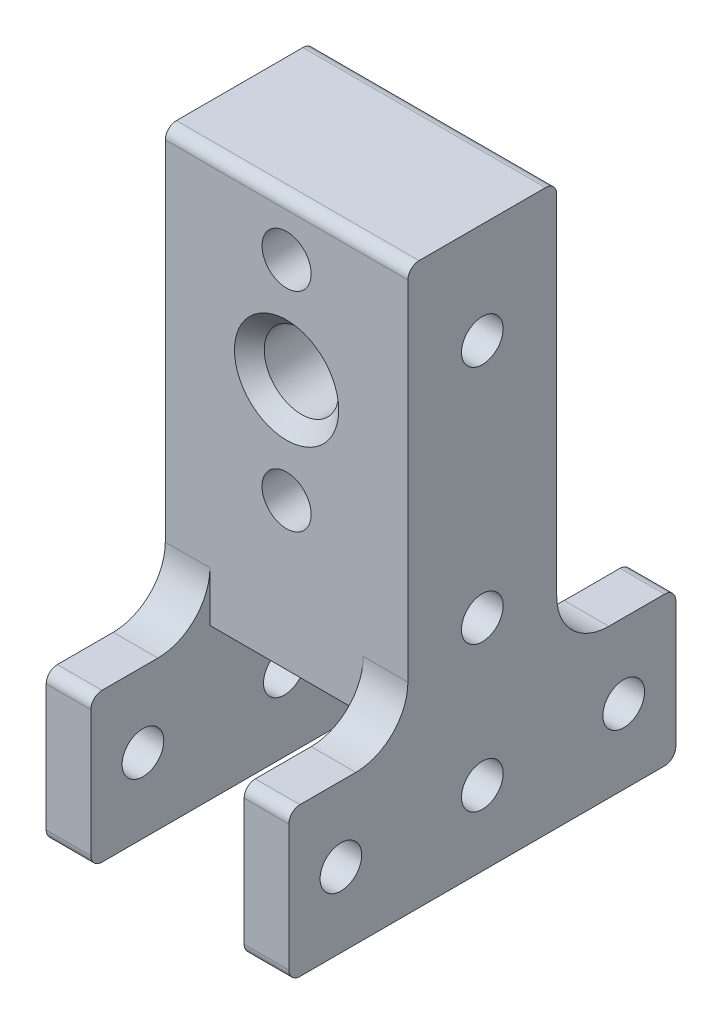
SolidWorks part; units mm, degrees
ref_plane "Front plane" through (0, 0, 0) normal (0, 0, 1) x (1, 0, 0)
ref_plane "Top plane" through (0, 0, 0) normal (0, 1, 0) x (1, 0, 0)
ref_plane "Right plane" through (0, 0, 0) normal (1, 0, 0) x (0, 0, -1)
ref_axis "Axis X" through (0, 0, 0) along (1, 0, 0)
ref_axis "Axis Y" through (0, 0, 0) along (0, 1, 0)
ref_axis "Axis Z" through (0, 0, 0) along (0, 0, 1)
sketch "Sketch1" plane through (0, 0, 0) normal (1, 0, 0) x (0, 0, -1)
  line L1 (10, 65.3) -> (-10, 65.3)
  line L2 (10, 65.3) -> (10, 10.3)
  line L3 (10, 10.3) -> (-10, 10.3)
  line L4 (-10, 65.3) -> (-10, 10.3)
  line L5 (10, 65.3) -> (-10, 10.3) construction
  line L6 (10, 10.3) -> (-10, 65.3) construction
  point P0 (0, 37.8)
  dimension "D1" = 10.3
  dimension "D2" = 20
  dimension "D3" = 55
extrude "Extrude1" add sketch "Sketch1" along normal blind 10.3 and the other way blind 10.3
sketch "Sketch2" plane through (10.3, 0, 0) normal (1, 0, 0) x (0, 0, -1)
  line L0 (10, 10.3) -> (10, 65.3) construction
  line L1 (26, 10) -> (17, 10)
  line L2 (26, 10) -> (26, -10)
  line L3 (26, -10) -> (-26, -10)
  line L4 (-26, 10) -> (-26, -10)
  line L5 (26, 10) -> (-26, -10) construction
  line L6 (26, -10) -> (-26, 10) construction
  line L7 (-10, 65.3) -> (10, 65.3)
  line L8 (-10, 65.3) -> (-10, 17)
  line L9 (-10, 10) -> (10, 10) construction
  line L10 (10, 65.3) -> (10, 17)
  line L11 (-17, 10) -> (-26, 10)
  line L12 (10, 10) -> (-10, 10) construction
  arc A0 (17, 10) -> (10, 17) centre (17, 17) cw
  arc A1 (-17, 10) -> (-10, 17) centre (-17, 17) ccw
  point P0 (0, 0)
  dimension "D3" = 7
  dimension "D1" = 20
  dimension "D2" = 52
extrude "Extrude2" add sketch "Sketch2" along normal blind 6
mirror "Mirror2" about plane through (0, 0, 0) normal (1, 0, 0) of "Extrude2"
sketch "Sketch4" plane through (16.3, 0, 0) normal (1, 0, 0) x (0, 0, -1)
  line L0 (0, 2.8) -> (0, -2.8) construction
  circle A0 centre (0, 0) radius 2.8
  circle A1 centre (19, 0) radius 2.8
  circle A2 centre (-19, 0) radius 2.8
  circle A3 centre (0, 19.5) radius 2.8
  circle A4 centre (0, 51.75) radius 2.8
  dimension "D1" = 5.6
  dimension "D2" = 5.6
  dimension "D4" = 5.6
  dimension "D5" = 5.6
  dimension "D3" = 19
  dimension "D6" = 32.25
  dimension "D7" = 19.5
extrude "Extrude3" cut sketch "Sketch4" against normal through all
sketch "Sketch5" plane through (0, 0, 10) normal (0, 0, 1) x (1, 0, 0)
  line L0 (-16.3, 19.5) -> (16.3, 19.5) construction
  line L1 (-16.3, 65.3) -> (-16.3, 17) construction
  line L2 (16.3, 65.3) -> (16.3, 17) construction
  line L3 (-16.3, 22.3) -> (16.3, 22.3) construction
  line L4 (-16.3, 16.7) -> (16.3, 16.7) construction
  line L5 (-16.3, 54.55) -> (16.3, 54.55) construction
  line L6 (-16.3, 51.75) -> (16.3, 51.75) construction
  line L7 (-16.3, 48.95) -> (16.3, 48.95) construction
  line L8 (-5, 44) -> (5, 44) construction
  line L9 (-10.3, 10) -> (10.3, 10) construction
  line L10 (-10.3, 10) -> (-10.3, -10) construction
  line L11 (10.3, 10) -> (10.3, -10) construction
  circle A0 centre (0, 44) radius 5
  dimension "D1" = 5.6
  dimension "D2" = 5.6
  dimension "D5" = 10
  dimension "D3" = 19.5
  dimension "D4" = 32.25
  dimension "D7" = 10
  dimension "D8" = 34
extrude "Extrude4" cut sketch "Sketch5" against normal through all
fillet "Fillet2" radius 1.5 10 edges at (13.3, -10, 26) (13.3, 10, 26) (-13.3, 10, 26) (-13.3, -10, 26) (-13.3, -10, -26) (13.3, -10, -26) (13.3, 10, -26) (-13.3, 10, -26) (0, 65.3, 10) (0, 65.3, -10)
chamfer "Chamfer1" distance 2 angle 45 2 edges at (5, 44, 10) (0, 49, -10)
sketch "Sketch7" plane through (0, 0, 10) normal (0, 0, 1) x (1, 0, 0)
  line L0 (-5, 44) -> (5, 44) construction
  circle A0 centre (0, 44) radius 5 construction
  circle A1 centre (0, 58) radius 1.95
  circle A2 centre (0, 30) radius 1.95
  dimension "D2" = 3.9
  dimension "D1" = 28
extrude "Extrude5" cut sketch "Sketch7" against normal through all
sketch "Sketch8" plane through (0, 0, 10) normal (0, 0, 1) x (1, 0, 0)
  circle A0 centre (0, 58) radius 3.3
  circle A1 centre (0, 30) radius 3.3
  dimension "D1" = 6.6
  dimension "D2" = 6.6
extrude "Extrude6" cut sketch "Sketch8" against normal offset from surface (8 mm away) 12 up to face at (0, 59.95, -10)
equation "\"bearing_d1\"= 5"
equation "\"bearing_d2\"= 10"
equation "\"print_offset\"= 0.6"
equation "\"bearing_h\"=15"
equation "\"prof_width\"= 20'Aluminium profile parameters"
equation "\"prof_groove\"= 6"
equation "\"prof_length\"= 410"
equation "\"prof_screw_diameter\"= 4"
equation "\"screw2_diameter\"= 2"
equation "\"screw2_diameter_ext\"= 4"
equation "\"screw2_heigh_head\"= 2"
equation "\"nut2_diameter\"= 4"
equation "\"nut2_heigh\"= 2"
equation "\"screw_offset_ext\"= 2"
equation "\"angle_heigh\"= 50'Angle mount parameters"
equation "\"angle_thikness\"= 3"
equation "\"angle_width\"= 30"
equation "\"mount_thikness\"= 15'Other mounts parameters"
equation "\"mount_screw\"= 4"
equation "\"mount_screw_distance\"= 40"
equation "\"bearings_distance\"= 22"
equation "\"tape_distance\"= 7.35"
equation "\"bearing_grove_d1\"= 4"
equation "\"bearing_grove_d2\"= 13"
equation "\"bearing_grove_h\"= 4"
equation "\"bearing_groove_r\"= 1"
equation "\"D1@Sketch1\"=(\"prof_width\"+\"print_offset\")/2"
equation "\"D3@Sketch1\"=55.00mm"
equation "\"D1@Extrude1\"=(\"prof_width\"+\"print_offset\")/2"
equation "\"D2@Extrude1\"=(\"prof_width\"+\"print_offset\")/2"
equation "\"D1@Sketch2\"=\"prof_width\""
equation "\"D1@Sketch4\"=\"print_offset\"+5"
equation "\"D2@Sketch4\"=\"D1@Sketch4\""
equation "\"D4@Sketch4\"=\"D1@Sketch4\""
equation "\"D5@Sketch4\"=\"D1@Sketch4\""
equation "\"D2@Sketch5\"=\"D1@Sketch5\""
equation "\"D1@Sketch5\"=\"print_offset\"+5.00mm"
equation "\"D7@Sketch5\"=\"prof_width\"/2"
equation "\"D2@Sketch7\"=\"print_offset\"*1.5+3"
equation "\"D1@Sketch8\"=\"print_offset\"+6.00mm"
equation "\"D2@Sketch8\"=\"D1@Sketch8\""
